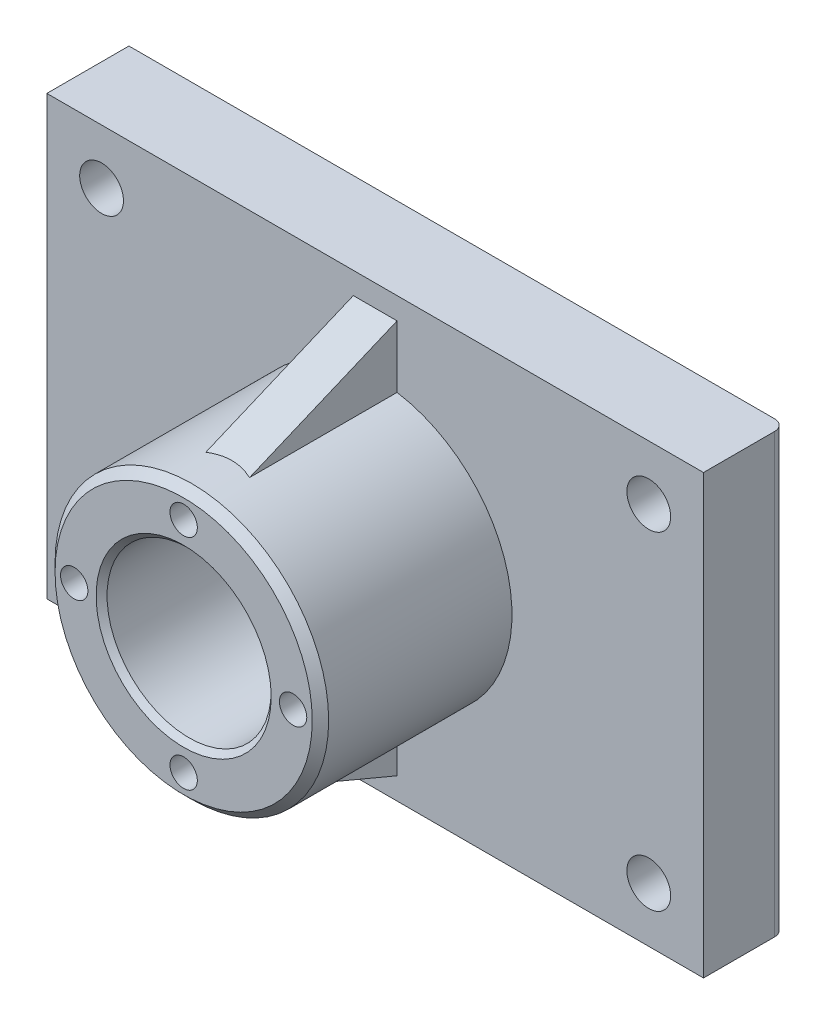
SolidWorks part; units mm, degrees
material "AISI 1020"
ref_plane "前视基准面" through (0, 0, 0) normal (0, 0, 1) x (1, 0, 0)
ref_plane "上视基准面" through (0, 0, 0) normal (0, 1, 0) x (1, 0, 0)
ref_plane "右视基准面" through (0, 0, 0) normal (1, 0, 0) x (0, 0, -1)
other "Configuration Table"
sketch "Sketch1" plane through (0, 0, 0) normal (0, 0, 1) x (1, 0, 0)
  line L1 (-60, -40) -> (60, -40)
  line L2 (-60, -40) -> (-60, 40)
  line L3 (-60, 40) -> (60, 40)
  line L4 (60, -40) -> (60, 40)
extrude "Boss-Extrude1" add sketch "Sketch1" along normal blind 15
sketch "Sketch2" plane through (0, 0, 15) normal (0, 0, 1) x (1, 0, 0)
  circle A0 centre (0, 0) radius 25
extrude "Boss-Extrude2" add sketch "Sketch2" along normal blind 35
sketch "Sketch3" plane through (0, 0, 50) normal (0, 0, 1) x (1, 0, 0)
  circle A0 centre (0, 0) radius 15
extrude "Cut-Extrude1" cut sketch "Sketch3" against normal through all
sketch "Sketch4" plane through (0, 0, 15) normal (0, 0, 1) x (1, 0, 0)
  circle A0 centre (-50, 30) radius 4
extrude "Cut-Extrude2" cut sketch "Sketch4" against normal through all
pattern_linear "LPattern1" count 2 spacing 100 along (1, 0, 0) of "Cut-Extrude2"
mirror "Mirror1" about plane through (0, 0, 0) normal (0, 1, 0) of "LPattern1", "Cut-Extrude2"
sketch "Sketch5" plane through (0, 0, 50) normal (0, 0, 1) x (1, 0, 0)
  circle A0 centre (20, 0) radius 2.5
extrude "Cut-Extrude3" cut sketch "Sketch5" against normal blind 12
ref_axis "Axis1" through (0, 0, 52.5) along (0, 0, -1)
pattern_circular "CirPattern1" count 4 over 360 about axis through (0, 0, 52.5) along (0, 0, -1) of "Cut-Extrude3"
chamfer "Chamfer1" distance 1.5 angle 45 1 edges at (25, 0, 50) tangent propagation no
chamfer "Chamfer2" distance 1 angle 45 1 edges at (15, 0, 50) tangent propagation no
sketch "Sketch6" plane through (0, 0, 0) normal (1, 0, 0) x (0, 0, -1)
  line L0 (40, 15) -> (25, 40)
sketch "Sketch7" plane through (0, 0, 0) normal (1, 0, 0) x (0, 0, -1)
  line L0 (-40, 15) -> (-25, 40)
sketch "Sketch8" plane through (0, 0, 0) normal (1, 0, 0) x (0, 0, -1)
  line L0 (-15, 36) -> (-40, 25.5)
rib "Rib6" sketch "Sketch8<2>" sketch "Sketch8<2>" thickness 8 extrusion direction parallel to sketch draft on no parameters "D1"=8
sketch "Sketch8<2>" plane through (0, 0, 0) normal (1, 0, 0) x (0, 0, -1) same geometry as "Sketch8"
sketch "Sketch9" plane through (0, 0, 0) normal (1, 0, 0) x (0, 0, -1)
  line L0 (-15, -36) -> (-40, -25.5)
rib "Rib7" sketch "Sketch9" sketch "Sketch9" thickness 8 extrusion direction parallel to sketch draft on no parameters "D1"=8
fillet "Fillet2" radius 2 1 edges at (60, 0, 0)
